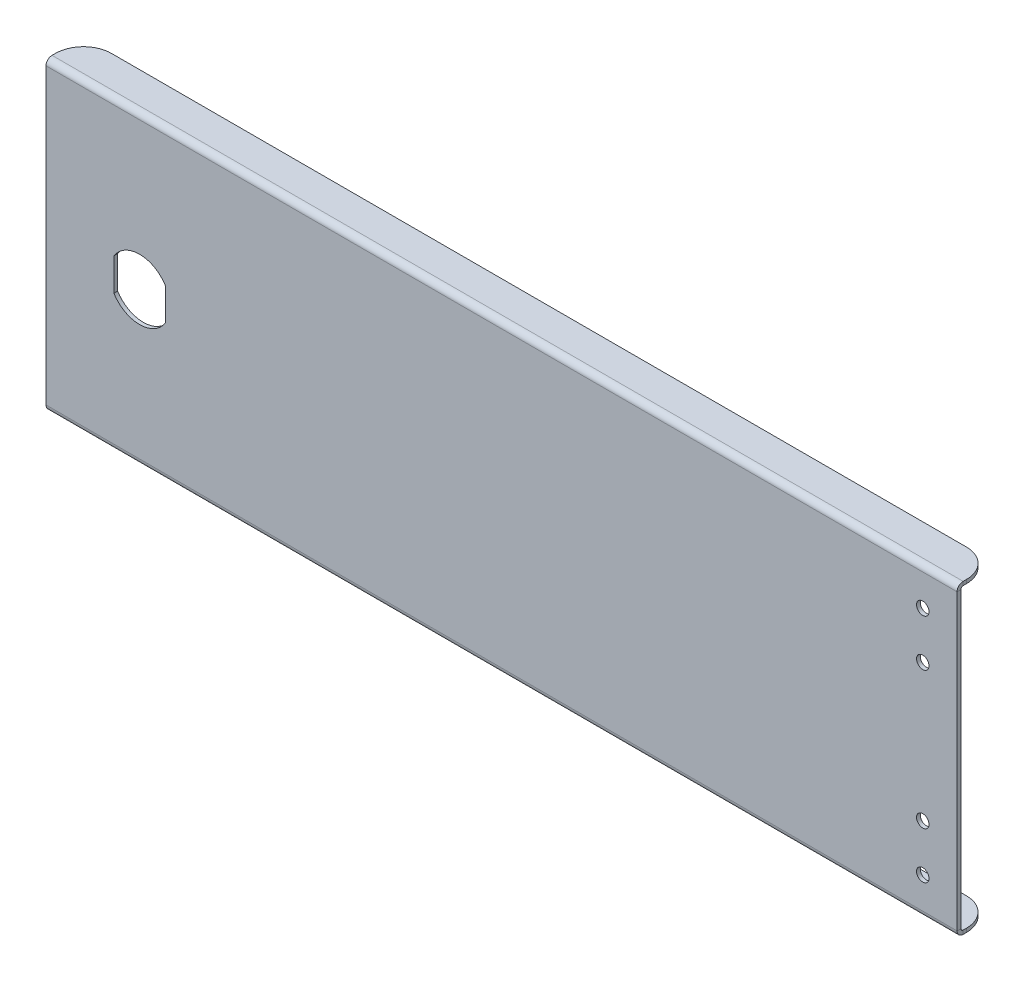
SolidWorks part; units mm, degrees
note: The reader was unsure of these and kept them because the rebuilt part matched: flange length of "Ребро-кромка1".
ref_plane "Спереди" through (0, 0, 0) normal (0, 0, 1) x (1, 0, 0)
ref_plane "Сверху" through (0, 0, 0) normal (0, 1, 0) x (1, 0, 0)
ref_plane "Справа" through (0, 0, 0) normal (1, 0, 0) x (0, 0, -1)
sketch "Эскиз1" plane through (0, 0, 0) normal (0, 0, 1) x (1, 0, 0)
  line L0 (0, 49) -> (30, 49) construction
  line L1 (0, 0) -> (292, 0)
  line L2 (0, 0) -> (0, 98)
  line L3 (0, 98) -> (292, 98)
  line L4 (292, 0) -> (292, 98)
  line L5 (21.75, 54.1962) -> (21.75, 43.8038)
  line L6 (281, 98) -> (281, 0) construction
  line L8 (38.25, 54.1962) -> (38.25, 43.8038)
  arc A0 (38.25, 54.1962) -> (21.75, 54.1962) centre (30, 49) ccw
  circle A1 centre (281, 86) radius 2
  circle A2 centre (281, 71) radius 2
  circle A3 centre (281, 27) radius 2
  circle A4 centre (281, 12) radius 2
  arc A5 (21.75, 43.8038) -> (38.25, 43.8038) centre (30, 49) ccw
  point P20 (38.25, 49)
  dimension "D3" = 19.5
  dimension "D6" = 15
  dimension "D7" = 15
  dimension "D8" = 12
  dimension "D9" = 12
  dimension "D10" = 4
  dimension "D1" = 98
  dimension "D2" = 292
  dimension "D4" = 30
  dimension "D5" = 11
  dimension "D11" = 16.5
  dimension "D12" = 8.25
base flange "Базовая кромка1" sketch "Эскиз1" thickness 1.2 reverse thickness direction no parameters "D1"=0.7366
edge flange "Ребро-кромка1" sketch "Эскиз10" flange profiles "Эскиз10", "Эскиз11" flange angle 90 flange length 12 flange position material inside bend radius 0.7366 thickness 1.2 relief rectangular parameters "D6"=10, "D8"=1
sketch "Эскиз10" plane through (0, 98, -1.2) normal (0, 1, 0) x (1, 0, 0)
  line L0 (292, 0) -> (0, 0) construction
  line L1 (292, 0) -> (0, 0)
  line L2 (0, 0) -> (0, 10.8)
  line L3 (0, 10.8) -> (292, 10.8)
  line L4 (292, 10.8) -> (292, 0)
sketch "Эскиз11" plane through (0, 0, -1.2) normal (0, -1, 0) x (-1, 0, 0)
  line L0 (0, 0) -> (-292, 0) construction
  line L1 (0, 0) -> (-292, 0)
  line L2 (-292, 0) -> (-292, 10.8)
  line L3 (-292, 10.8) -> (0, 10.8)
  line L4 (0, 10.8) -> (0, 0)
bend "EdgeBend1" bend radius 0.7366 bend angle 90 parameters "D5"=1
bend "EdgeBend2" bend radius 0.7366 bend angle 90 parameters "D5"=2
sketch "Эскиз12" plane through (0, 98, 0) normal (0, 1, 0) x (1, 0, 0)
  line L1 (0, 1.2) -> (0, 12) construction
  line L2 (292, 12) -> (0, 12) construction
  line L3 (9, 12) -> (0, 12)
  line L4 (0, 12) -> (0, 3)
  line L5 (283, 12) -> (292, 12)
  line L6 (292, 12) -> (292, 3)
  line L7 (292, 1.9366) -> (292, 12) construction
  arc A0 (0, 3) -> (9, 12) centre (9, 3) cw
  arc A1 (283, 12) -> (292, 3) centre (283, 3) cw
  dimension "D1" = 9
extrude "Вырез-Вытянуть1" cut sketch "Эскиз12" against normal through all normal cut yes
sketch "Сгиб-Линии1" plane through (0, 0, 0) normal (0, 1, 0) x (1, 0, 0)
sketch "Граничная рамка1" plane through (0, 0, 0) normal (0, 1, 0) x (1, 0, 0)
sheet metal parameters "Листовой металл3" thickness 1.2 parameters "D1"=0.7366
flat pattern "Развертка3" [suppressed]
sketch "Сгиб-Линии2" plane through (0, 0, 0) normal (0, 1, 0) x (1, 0, 0)
sketch "Граничная рамка2" [suppressed] plane through (0, 0, 0) normal (0, 1, 0) x (1, 0, 0)
sheet metal parameters "Листовой металл4" thickness 1.2 parameters "D1"=0.7366
flat pattern "Развертка3" [suppressed]
sketch "Сгиб-Линии2" plane through (0, 0, 0) normal (0, 1, 0) x (1, 0, 0)
sketch "Граничная рамка2" [suppressed] plane through (0, 0, 0) normal (0, 1, 0) x (1, 0, 0)
bend of the flat pattern "Плоское состояние-<EdgeBend1>1"
bend of the flat pattern "Плоское состояние-<EdgeBend2>1"
sheet metal parameters "Листовой металл5" thickness 1.2 parameters "D1"=0.7366
flat pattern "Развертка3" [suppressed]
sketch "Сгиб-Линии2" plane through (0, 0, 0) normal (0, 1, 0) x (1, 0, 0)
sketch "Граничная рамка2" [suppressed] plane through (0, 0, 0) normal (0, 1, 0) x (1, 0, 0)
bend of the flat pattern "Плоское состояние-<EdgeBend1>1"
bend of the flat pattern "Плоское состояние-<EdgeBend2>1"
